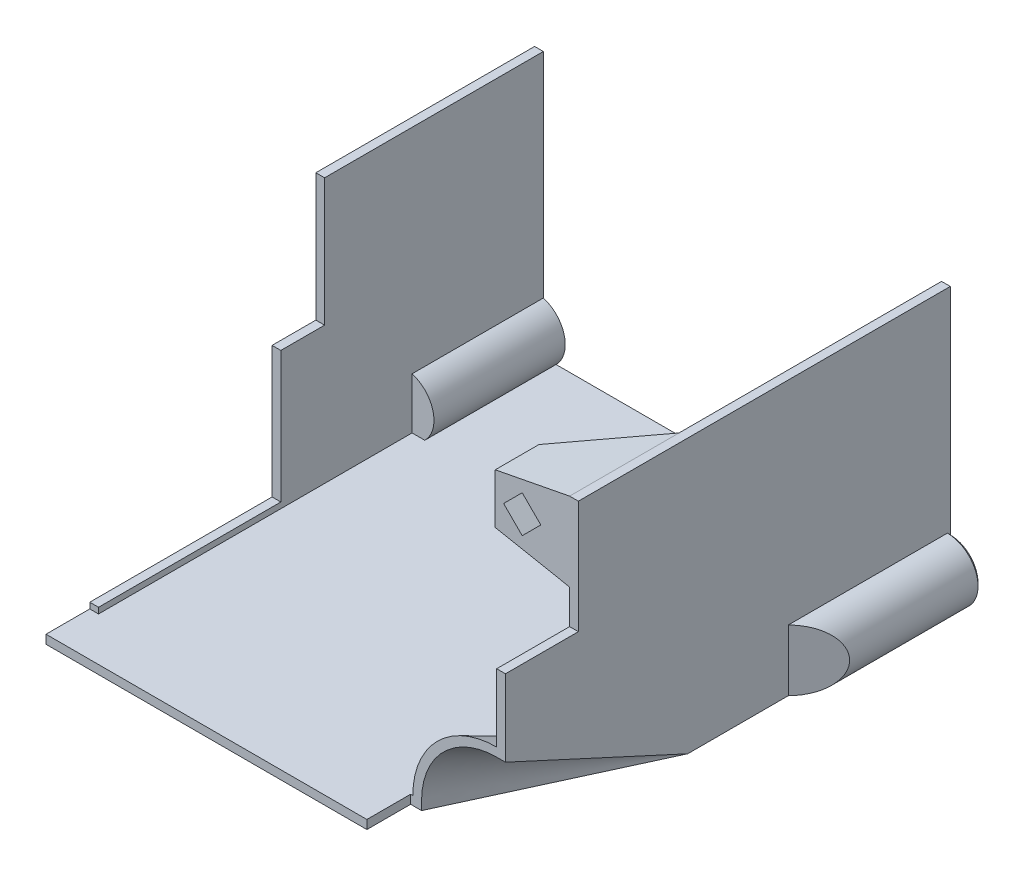
SolidWorks part; units mm, degrees
material "Custom Plastic"
ref_plane "Front Plane" through (0, 0, 0) normal (0, 0, 1) x (1, 0, 0)
ref_plane "Top Plane" through (0, 0, 0) normal (0, 1, 0) x (1, 0, 0)
ref_plane "Right Plane" through (0, 0, 0) normal (1, 0, 0) x (0, 0, -1)
sketch "Sketch1" plane through (0, 0, 0) normal (0, 0, 1) x (1, 0, 0)
  line L1 (-33.6475, 16.5475) -> (-34.8475, 16.5475)
  line L2 (-33.6475, -19.7525) -> (-33.6475, -20.9525) construction
  line L3 (-31.9081, -19.7525) -> (19.2131, -19.7525)
  line L4 (20.9525, 16.5475) -> (20.9525, -12.7276)
  line L5 (-33.6475, -12.7276) -> (-33.6475, 16.5475)
  line L7 (20.9525, 16.5475) -> (22.1525, 16.5475)
  line L8 (-34.8475, 16.5475) -> (-34.8475, -12.5525)
  line L9 (-34.8475, -20.9525) -> (22.1525, -20.9525)
  line L10 (22.1525, 16.5475) -> (22.1525, -12.5525)
  arc A0 (22.1525, -20.9525) -> (22.1525, -12.5525) centre (22.1525, -16.7525) ccw
  circle A1 centre (22.1525, -16.7525) radius 1.6 construction
  arc A2 (20.9525, -12.7276) -> (19.2131, -19.7525) centre (22.1525, -16.7525) ccw
  circle A3 centre (-34.8475, -16.7525) radius 1.6 construction
  arc A4 (-34.8475, -12.5525) -> (-34.8475, -20.9525) centre (-34.8475, -16.7525) ccw
  arc A6 (-31.9081, -19.7525) -> (-33.6475, -12.7276) centre (-34.8475, -16.7525) ccw
  dimension "D2" = 3.2
  dimension "D5" = 4.2
  dimension "D1" = 1.2
  dimension "D3" = 57
  dimension "D4" = 37.5
extrude "Boss-Extrude1" add sketch "Sketch1" along normal blind 67
sketch "Sketch2" plane through (0, 0, 67) normal (0, 0, 1) x (1, 0, 0)
  line L0 (-34.8475, -20.9525) -> (22.1525, -20.9525) construction
  line L1 (9.1525, -20.9525) -> (32.8781, -20.9525)
  line L2 (9.1525, -20.9525) -> (9.1525, -19.7525)
  line L3 (-34.8475, 12.6741) -> (32.8781, 12.6741)
  line L4 (32.8781, -20.9525) -> (32.8781, 12.6741)
  line L5 (22.1525, -12.5525) -> (22.1525, 16.5475) construction
  line L6 (9.1525, -19.7525) -> (-34.8475, -19.7525)
  line L7 (19.2131, -19.7525) -> (-31.9081, -19.7525) construction
  line L8 (-34.8475, 16.5475) -> (-34.8475, -12.5525) construction
  line L9 (-34.8475, -20.9525) -> (-34.8475, -19.7525)
  line L10 (-34.8475, -20.9525) -> (-42.7406, -20.9525)
  line L11 (-34.8475, -20.9525) -> (22.1525, -20.9525) construction
  line L12 (-42.7406, -20.9525) -> (-42.7406, -7.5075)
  line L13 (-42.7406, -7.5075) -> (-34.8475, -7.5075)
  line L14 (-34.8475, -7.5075) -> (-34.8475, 12.6741)
  dimension "D1" = 13
extrude "Cut-Extrude1" cut sketch "Sketch2" against normal blind 6
sketch "Sketch3" plane through (0, 0, 61) normal (0, 0, 1) x (1, 0, 0)
  line L0 (22.1525, -12.5525) -> (22.1525, 12.6741) construction
  line L1 (-34.8475, 16.5475) -> (22.1525, 16.5475)
  line L2 (-34.8475, 16.5475) -> (-34.8475, 1.0475)
  line L3 (-34.8475, 1.0475) -> (22.1525, 1.0475)
  line L4 (22.1525, 16.5475) -> (22.1525, 1.0475)
  dimension "D1" = 15.5
extrude "Cut-Extrude2" cut sketch "Sketch3" against normal blind 10 and the other way blind 10
sketch "Sketch4" plane through (0, 0, 51) normal (0, 0, 1) x (1, 0, 0)
  line L0 (-34.8475, 16.5475) -> (-34.8475, 1.0475) construction
  line L1 (-34.8475, 16.5475) -> (-33.6475, 16.5475)
  line L2 (-34.8475, 16.5475) -> (-34.8475, -0.9525)
  line L3 (-34.8475, -0.9525) -> (-33.6475, -0.9525)
  line L4 (-33.6475, 16.5475) -> (-33.6475, -0.9525)
extrude "Cut-Extrude3" cut sketch "Sketch4" against normal blind 21
sketch "Sketch6" plane through (0, 0, 0) normal (0, 0, -1) x (-1, 0, 0)
  circle A0 centre (-22.1525, -16.7525) radius 1.6
  circle A1 centre (34.8475, -16.7525) radius 1.6
  arc A2 (34.8475, -20.9525) -> (34.8475, -12.5525) centre (34.8475, -16.7525) ccw construction
  arc A3 (-22.1525, -12.5525) -> (-22.1525, -20.9525) centre (-22.1525, -16.7525) ccw construction
  dimension "D1" = 3.2
extrude "Cut-Extrude4" cut sketch "Sketch6" against normal blind 16
sketch "Sketch7" plane through (0, 0, 61) normal (0, 0, 1) x (1, 0, 0)
  line L0 (19.2131, -19.7525) -> (9.1525, -19.7525) construction
  line L1 (22.1525, -12.5525) -> (31.8181, -12.5525)
  line L2 (22.1525, -12.5525) -> (22.1525, -20.9525)
  line L3 (22.1525, -20.9525) -> (31.8181, -20.9525)
  line L4 (31.8181, -12.5525) -> (31.8181, -20.9525)
  line L5 (20.9525, -12.7276) -> (15.0843, -12.7276)
  line L6 (20.9525, -12.7276) -> (20.9525, -19.7525)
  line L7 (20.9525, -19.7525) -> (15.0843, -19.7525)
  line L8 (15.0843, -12.7276) -> (15.0843, -19.7525)
  line L9 (-33.6475, -12.7276) -> (-33.6475, 1.0475) construction
  line L10 (-34.8475, -20.9525) -> (-44.0251, -20.9525)
  line L11 (-34.8475, -20.9525) -> (-34.8475, -7.6032)
  line L12 (-34.8475, -7.6032) -> (-44.0251, -7.6032)
  line L13 (-44.0251, -20.9525) -> (-44.0251, -7.6032)
  line L14 (-33.6475, -7.6032) -> (-26.816, -7.6032)
  line L15 (-33.6475, -7.6032) -> (-33.6475, -19.7525)
  line L16 (-33.6475, -19.7525) -> (-26.816, -19.7525)
  line L17 (-26.816, -7.6032) -> (-26.816, -19.7525)
  line L18 (9.1525, -19.7525) -> (-34.8475, -19.7525) construction
extrude "Cut-Extrude5" cut sketch "Sketch7" against normal offset from surface (43 mm away) 18 up to face at (-36.4475, -16.7525, 0)
chamfer "Chamfer1" distance 4.2 angle 45 2 edges at (22.1525, -16.7525, 18) (-34.8475, -16.7525, 18)
chamfer "Chamfer3" distance 0.6 angle 30 2 edges at (20.5525, -16.7525, 0) (-36.4475, -16.7525, 0) first distance on face at (20.5525, -16.7525, 16) first distance on face at (-36.4475, -16.7525, 16)
chamfer "Chamfer4" distance 0.4 angle 45 3 edges at (-39.0475, -16.7525, 0) (-6.3475, -20.9525, 0) (26.3525, -16.7525, 0)
sketch "Sketch8" plane through (0, 0, 51) normal (0, 0, 1) x (1, 0, 0)
  line L0 (14.4525, 12.7475) -> (10.7525, 12.7475) construction
  line L1 (11.9025, 11.1475) -> (14.4525, 13.6975)
  line L2 (10.7525, 9.5475) -> (14.4525, 9.5475) construction
  line L4 (10.7525, 14.5725) -> (10.7525, 12.7475)
  line L5 (10.7525, 9.5475) -> (10.7525, 7.7225)
  line L7 (20.9525, 16.5475) -> (20.9525, 1.0475) construction
  line L8 (20.9525, 5.7475) -> (22.1525, 5.7475)
  line L9 (22.1525, 1.0475) -> (22.1525, 16.5475) construction
  line L10 (22.1525, 5.7475) -> (22.1525, 16.5475)
  line L11 (22.1525, 16.5475) -> (20.9525, 16.5475)
  line L12 (11.9025, 11.1475) -> (14.4525, 8.5975)
  line L13 (14.4525, 13.6975) -> (17.0025, 11.1475)
  line L14 (14.4525, 8.5975) -> (17.0025, 11.1475)
  line L15 (11.9025, 11.1475) -> (22.1525, 11.1475) construction
  line L16 (14.4525, 13.6975) -> (14.4525, 8.5975) construction
  line L17 (10.7525, 12.7475) -> (10.7525, 9.5475)
  line L18 (20.9525, 16.5475) -> (10.7525, 14.5725)
  line L19 (20.9525, 5.7475) -> (10.7525, 7.7225)
  arc A0 (14.4525, 9.5475) -> (14.4525, 12.7475) centre (14.4525, 11.1475) ccw construction
  circle A1 centre (14.4525, 11.1475) radius 2.55 construction
  dimension "D1" = 1.6
  dimension "D5" = 5.1
  dimension "D2" = 6.5
  dimension "D3" = 5.4
  dimension "D4" = 10.2
  dimension "D6" = 6.85
extrude "Boss-Extrude2" add sketch "Sketch8" against normal blind 15
sketch "Sketch10" plane through (0, 0, 36) normal (0, 0, -1) x (-1, 0, 0)
  line L0 (-14.4525, 14.1475) -> (-10.7525, 14.1475)
  line L1 (-10.7525, 14.5725) -> (-10.7525, 7.7225) construction
  line L2 (-10.7525, 14.1475) -> (-10.7525, 8.1475)
  line L3 (-10.7525, 8.1475) -> (-14.4525, 8.1475)
  line L5 (-14.4525, 13.6975) -> (-14.4525, 8.5975) construction
  arc A0 (-14.4525, 14.1475) -> (-14.4525, 8.1475) centre (-14.4525, 11.1475) ccw
  arc A1 (-14.4525, 8.1475) -> (-14.4525, 14.1475) centre (-14.4525, 11.1475) ccw construction
  dimension "D1" = 3
extrude "Cut-Extrude6" cut sketch "Sketch10" against normal offset from surface 6 and the other way blind 10 up to face at (18.3811, 9.0332, 51)
sketch "Sketch11" plane through (0, 16.5475, 0) normal (0, 1, 0) x (1, 0, 0)
  line L0 (20.9525, -36) -> (10.7525, -45)
  line L1 (10.7525, -36) -> (10.7525, -51) construction
  line L2 (10.7525, -45) -> (10.7525, -36)
  line L3 (10.7525, -36) -> (20.9525, -36)
extrude "Cut-Extrude7" cut sketch "Sketch11" against normal up to surface and the other way blind 10 up to face at (15.8525, 6.735, 43.5)
sketch "Sketch12" plane through (0, 1.0475, 0) normal (0, 1, 0) x (1, 0, 0)
  line L0 (-34.8475, -61) -> (-34.8475, -51) construction
  line L1 (-34.8475, -36) -> (-33.6475, -36)
  line L2 (-34.8475, -36) -> (-34.8475, -61)
  line L3 (-34.8475, -61) -> (-33.6475, -61)
  line L4 (-33.6475, -36) -> (-33.6475, -61)
  line L5 (-33.6475, -30) -> (-34.8475, -30) construction
  point P7 (-34.2475, -30)
  dimension "D1" = 6
extrude "Cut-Extrude8" cut sketch "Sketch12" against normal offset from surface (20 mm away) 0.8 up to face at (-8.5141, -19.7525, 37.5)
sketch "Sketch13" plane through (0, 0, 61) normal (0, 0, 1) x (1, 0, 0)
  line L0 (20.9525, 1.0475) -> (20.9525, -19.7525) construction
  line L1 (20.9525, -19.7525) -> (9.1525, -19.7525) construction
  line L2 (9.4525, -19.7525) -> (20.9525, -19.7525)
  line L3 (20.9525, -19.7525) -> (20.9525, -8.2525)
  arc A0 (20.9525, -8.2525) -> (9.4525, -19.7525) centre (20.9525, -19.7525) ccw
  dimension "D1" = 11.5
sketch "Sketch14" plane through (20.9525, 0, 0) normal (-1, 0, 0) x (0, 0, 1)
  line L0 (18, -19.7525) -> (61, -19.7525) construction
  line L1 (61, 1.0475) -> (61, -19.7525) construction
  point P0 (36, -19.7525)
  dimension "D1" = 25
loft "Loft1" add profiles "Sketch13", "Sketch14"
sketch "Sketch15" plane through (0, 0, 61) normal (0, 0, 1) x (1, 0, 0)
  line L2 (20.9525, -9.4525) -> (22.1525, -9.4525)
  line L4 (22.1525, -20.9525) -> (22.1525, -12.5525) construction
  line L5 (22.1525, -9.4525) -> (22.1525, -20.9525)
  line L6 (22.1525, -20.9525) -> (10.6525, -20.9525)
  line L7 (9.1525, -20.9525) -> (22.1525, -20.9525) construction
  line L8 (10.6525, -20.9525) -> (10.6525, -19.7525)
  line L9 (20.9525, -9.4525) -> (20.9525, -8.2525) construction
  line L10 (20.9525, -8.2525) -> (22.1525, -8.2525) construction
  line L11 (22.1525, -20.9525) -> (22.1525, 1.0475) construction
  arc A0 (20.9525, -9.4525) -> (10.6525, -19.7525) centre (20.9525, -19.7525) ccw
  arc A1 (22.1525, -20.9525) -> (26.3525, -16.7525) centre (22.1525, -16.7525) ccw construction
sketch "Sketch16" plane through (22.1525, 0, 0) normal (1, 0, 0) x (0, 0, -1)
  line L0 (-61, -20.9525) -> (-22.2, -20.9525) construction
  point P0 (-36, -20.9525)
loft "Cut-Loft1" cut profiles "Sketch15", "Sketch16"
